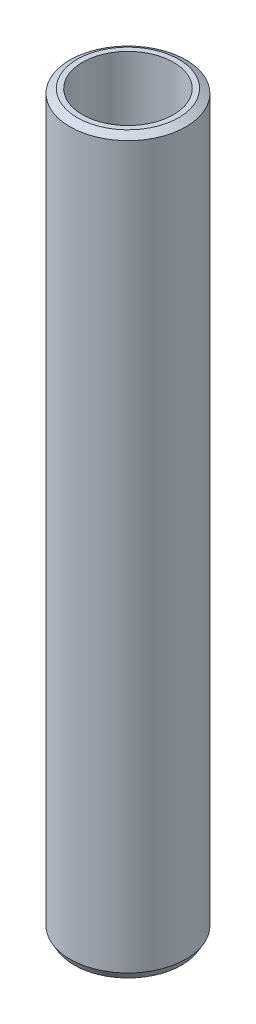
SolidWorks part; units mm, degrees
ref_plane "Front Plane" through (0, 0, 0) normal (0, 0, 1) x (1, 0, 0)
ref_plane "Top Plane" through (0, 0, 0) normal (0, 1, 0) x (1, 0, 0)
ref_plane "Right Plane" through (0, 0, 0) normal (1, 0, 0) x (0, 0, -1)
sketch "Sketch1" plane through (0, 0, 0) normal (0, 1, 0) x (1, 0, 0)
  circle A0 centre (0, 0) radius 47.5
  dimension "SHAFT_OD" = 95
extrude "Boss-Extrude1" add sketch "Sketch1" along normal blind 600
sketch "Sketch2" plane through (0, 0, 0) normal (0, 1, 0) x (1, 0, 0)
  circle A0 centre (0, 0) radius 37.2602
  dimension "BORE_D" = 74.5203
extrude "Cut-Extrude1" cut sketch "Sketch2" along normal through all
chamfer "Chamfer1" distance 3.4554 angle 60 2 edges at (0, 600, 47.5) (0, 0, 47.5) first distance on face at (0, 600, 47.5) first distance on face at (0, 0, 37.2602)
